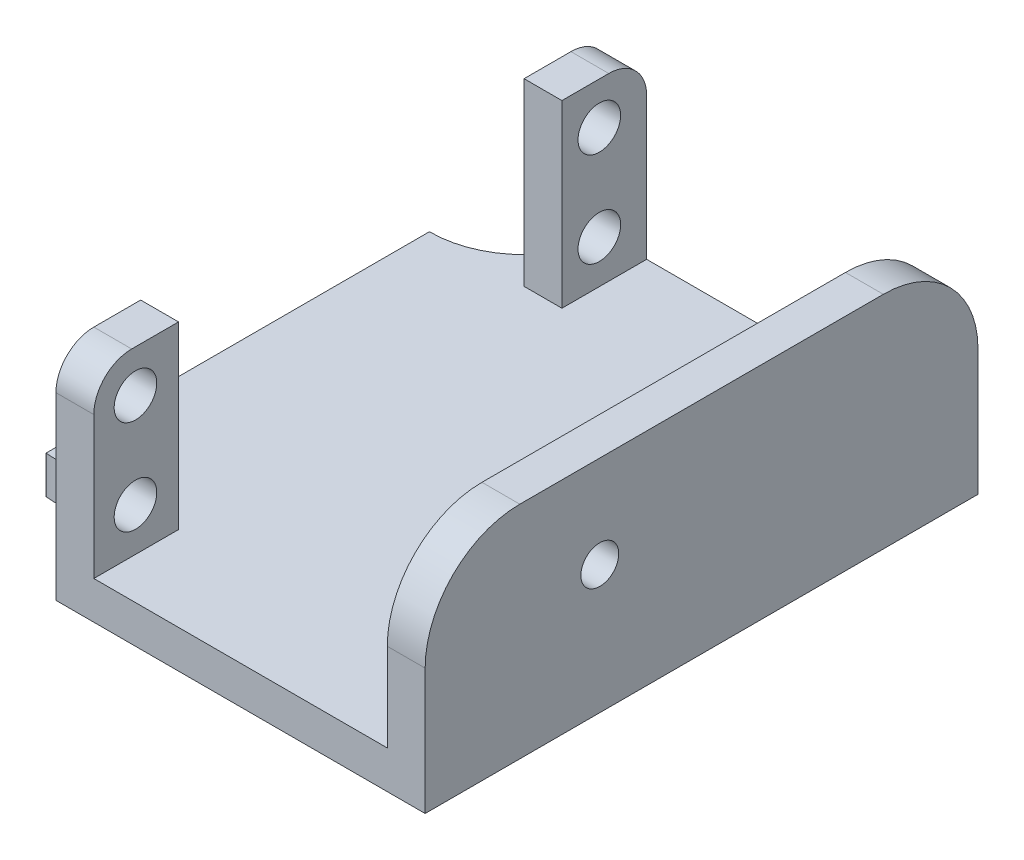
SolidWorks part; units mm, degrees
material "PLA"
ref_plane "Front Plane" through (0, 0, 0) normal (0, 0, 1) x (1, 0, 0)
ref_plane "Top Plane" through (0, 0, 0) normal (0, 1, 0) x (1, 0, 0)
ref_plane "Right Plane" through (0, 0, 0) normal (1, 0, 0) x (0, 0, -1)
sketch "Sketch1" plane through (0, 0, 0) normal (0, 1, 0) x (1, 0, 0)
  line L0 (-49, 49.45) -> (-39, 49.45)
  line L1 (-39, 49.45) -> (-39, 58.4)
  line L2 (-39, 58.4) -> (0, 58.4)
  line L3 (0, 58.4) -> (0, 0)
  line L4 (0, 0) -> (-39, 0)
  line L5 (-39, 0) -> (-39, 8.95)
  line L6 (-39, 8.95) -> (-49, 8.95)
  line L7 (-49, 8.95) -> (-49, 49.45)
  dimension "D1" = 58.4
  dimension "D2" = 49
  dimension "D3" = 10
  dimension "D4" = 8.95
  dimension "D5" = 8.95
extrude "Boss-Extrude1" add sketch "Sketch1" along normal blind 4
sketch "Sketch2" plane through (-39, 0, 0) normal (-1, 0, 0) x (0, 0, 1)
  line L0 (-58.4, 4) -> (-49.45, 4) construction
  line L1 (-8.95, 23) -> (0, 23)
  line L2 (-8.95, 23) -> (-8.95, 4)
  line L3 (-8.95, 4) -> (0, 4)
  line L4 (0, 23) -> (0, 4)
  line L5 (-58.4, 23) -> (-49.45, 23)
  line L6 (-58.4, 23) -> (-58.4, 4)
  line L7 (-58.4, 4) -> (-49.45, 4)
  line L8 (-49.45, 23) -> (-49.45, 4)
  line L9 (-58.4, 4) -> (-58.4, 0) construction
  line L10 (-49.45, 4) -> (-49.45, 0) construction
  line L11 (-8.95, 4) -> (0, 4) construction
  line L12 (0, 4) -> (0, 0) construction
  line L13 (-8.95, 4) -> (-8.95, 0) construction
  line L14 (-49.45, 4) -> (-8.95, 4) construction
  circle A0 centre (-4.4, 18.55) radius 2.25
  circle A1 centre (-4.4, 8.55) radius 2.25
  circle A2 centre (-53.4, 18.55) radius 2.25
  circle A3 centre (-53.4, 8.55) radius 2.25
  dimension "D1" = 4.5
  dimension "D2" = 4.5
  dimension "D8" = 4.5
  dimension "D9" = 4.5
  dimension "D3" = 19
  dimension "D4" = 10
  dimension "D5" = 3.95
  dimension "D6" = 4.55
  dimension "D7" = 3.95
  dimension "D10" = 4.55
extrude "Boss-Extrude2" add sketch "Sketch2" against normal blind 4
fillet "Fillet1" radius 10 2 edges at (-39, 2, -49.45) (-39, 2, -8.95)
fillet "Fillet2" radius 4 2 edges at (-37, 23, -58.4) (-37, 23, 0)
sketch "Sketch3" plane through (0, 0, 0) normal (1, 0, 0) x (0, 0, -1)
  line L0 (0, 4) -> (58.4, 4) construction
  line L1 (0, 23.3) -> (58.4, 23.3)
  line L2 (0, 23.3) -> (0, 4)
  line L3 (0, 4) -> (58.4, 4)
  line L4 (58.4, 23.3) -> (58.4, 4)
  line L5 (0, 4) -> (0, 0) construction
  line L6 (58.4, 4) -> (58.4, 0) construction
  circle A0 centre (18.45, 13.55) radius 2
  dimension "D4" = 4
  dimension "D1" = 19.3
  dimension "D2" = 18.45
  dimension "D3" = 9.75
extrude "Boss-Extrude3" add sketch "Sketch3" against normal blind 4
fillet "Fillet3" radius 10 2 edges at (-2, 23.3, 0) (-2, 23.3, -58.4)
